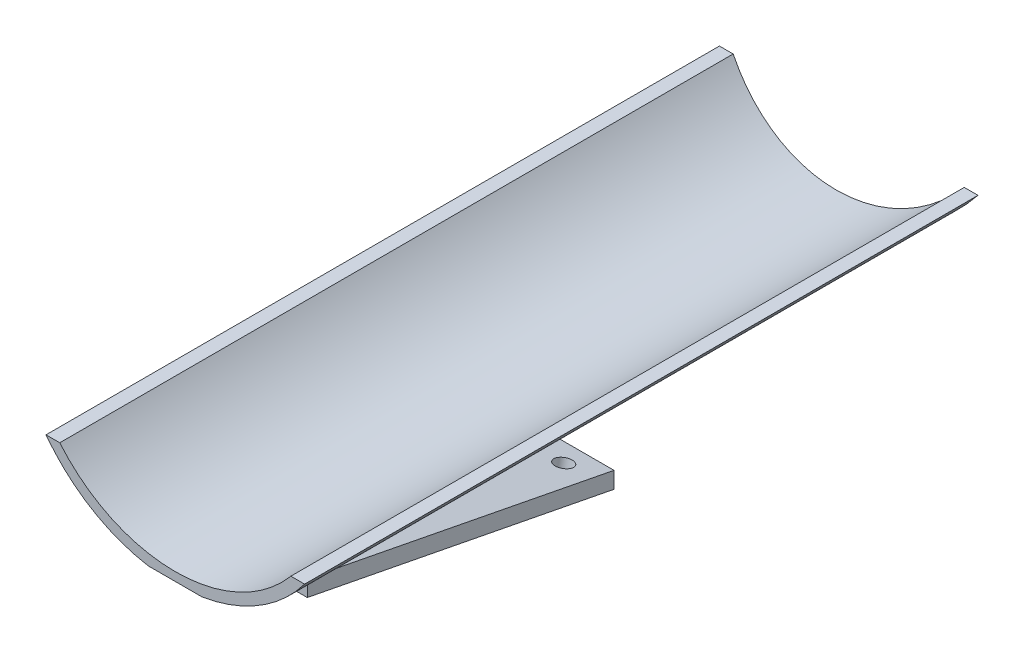
SolidWorks part; units mm, degrees
ref_plane "Front Plane" through (0, 0, 0) normal (0, 0, 1) x (1, 0, 0)
ref_plane "Top Plane" through (0, 0, 0) normal (0, 1, 0) x (1, 0, 0)
ref_plane "Right Plane" through (0, 0, 0) normal (1, 0, 0) x (0, 0, -1)
ref_axis "Axis1" through (0, -34.3594, 0) along (0, 1, 0)
ref_axis "Axis2" through (-26.4, 0, 0) along (1, 0, 0)
sketch "Sketch1" plane through (0, 0, 0) normal (0, 0, 1) x (1, 0, 0)
  line L0 (-24, 0) -> (-21.4476, 0)
  line L1 (21.4476, 0) -> (24, 0)
  line L2 (5, -11.5804) -> (-5, -11.5804)
  arc A0 (-24, 0) -> (-5, -11.5804) centre (0, 18) ccw
  arc A1 (21.4476, 0) -> (-21.4476, 0) centre (0, 18) cw
  arc A2 (5, -11.5804) -> (24, 0) centre (0, 18) ccw
  dimension "D1" = 28
  dimension "D2" = 30
  dimension "D3" = 18
  dimension "D4" = 10
extrude "Main" add sketch "Sketch1" along normal blind 125
ref_plane "CutPlane" through (0, 0, 0) normal (0, 0.225, 0.9744) x (1, 0, 0)
sketch "Sketch2" plane through (0, 0, 0) normal (0, 0.225, 0.9744) x (1, 0, 0)
  circle A0 centre (0, 0) radius 25
  point P2 (0.8432, 0)
  point P3 (0, 0)
  dimension "D1" = 50
extrude "BehindCut" cut sketch "Sketch2" against normal through all
sketch "Sketch4" plane through (0, 0, 0) normal (1, 0, 0) x (0, 0, -1)
  line L0 (-113, -11.5804) -> (-56.0656, -11.5804)
  line L1 (-56.0656, -11.5804) -> (-56.0656, -24.9799)
  line L2 (-56.0656, -24.9799) -> (-113, -13.913)
  line L3 (-113, -13.913) -> (-113, -11.5804)
  line L5 (-2.6735, -11.5804) -> (-2.6735, -35.3583) construction
  line L6 (6.5326, 28.2957) -> (-6.5326, -28.2957) construction
  line L7 (-125, -11.5804) -> (-2.6735, -11.5804) construction
  point P2 (-3.3421, -11.5804)
  point P6 (-2.1955, -11.5804)
  point P7 (-56.2674, -11.5804)
  point P8 (-56.2674, -25.3258)
  point P15 (-3.198, -38.6492)
  point P16 (0, 0)
  point P17 (-115.3775, -11.5804)
  point P19 (-45.7608, -32.001)
  point P20 (-105, -11.5804)
  point P21 (-45.7838, -11.5804)
  point P22 (0, 0)
  point P23 (0, 0)
  point P25 (-56.2674, -25.3258)
  point P26 (-56.2674, -11.5804)
  point P29 (-113, -13.2669)
  point P30 (-113, -11.5804)
  point P31 (-113, -13.4538)
  dimension "D1" = 11
  dimension "D2" = 58
  dimension "D3" = 12
  dimension "D4" = 23.7779
  dimension "D5" = 13.3995
extrude "CentralSupport" add sketch "Sketch4" along normal mid plane 5
sketch "Sketch5" plane through (0, 0, 0) normal (1, 0, 0) x (0, 0, -1)
  line L0 (-56.0656, -24.9799) -> (-113, -13.913)
  line L1 (-113, -13.913) -> (-113, -11.5804)
  line L2 (-109.2775, -11.5804) -> (-56.0656, -21.9237)
  line L3 (-113, -13.913) -> (-56.0656, -24.9799) construction
  line L4 (-56.0656, -21.9237) -> (-56.0656, -24.9799)
  line L5 (-56.0656, -24.9799) -> (-56.0656, -11.5804) construction
  line L9 (-56.0656, -11.5804) -> (-113, -11.5804) construction
  line L10 (-113, -11.5804) -> (-109.2775, -11.5804)
  line L11 (-113, -11.5804) -> (-113, -13.913) construction
  point P6 (-113, -12.087)
  point P11 (-56.0656, -24.3163)
  point P12 (-56.0656, -24.9247)
  point P15 (-56.0656, -24.9799)
  dimension "D2" = 3
extrude "SideSupport" add sketch "Sketch5" along normal mid plane 25
sketch "Sketch6" plane through (0, -34.5717, 6.7201) normal (0, -0.9816, 0.1908) x (-1, 0, 0)
  line L0 (-2.5, -120.4938) -> (-2.5, -50.2692) construction
  line L1 (-12.5, -50.2692) -> (12.5, -50.2692) construction
  line L2 (2.5, -120.4938) -> (2.5, -50.2692) construction
  circle A0 centre (7.5, -55.2692) radius 1.6
  circle A1 centre (-7.5, -55.2692) radius 1.6
  point P4 (0, 0)
  dimension "D1" = 3.2
  dimension "D2" = 5
  dimension "D3" = 5
  dimension "D4" = 5
extrude "HoleFix" cut sketch "Sketch6" against normal up to next
sketch "Sketch9" plane through (0, -34.5717, 6.7201) normal (0, -0.9816, 0.1908) x (-1, 0, 0)
  line L0 (-12.5, -50.2692) -> (12.5, -50.2692) construction
  line L1 (2.5, -50.2692) -> (-2.5, -50.2692)
  line L2 (2.5, -50.2692) -> (2.5, -108.2692)
  line L3 (2.5, -108.2692) -> (-2.5, -108.2692)
  line L4 (-2.5, -50.2692) -> (-2.5, -108.2692)
  line L5 (-12.5, -108.2692) -> (12.5, -108.2692) construction
  line L6 (2.5, -50.8523) -> (2.5, -52.8259) construction
  line L7 (-2.5, -50.8523) -> (-2.5, -52.8259) construction
extrude "Boss-Extrude4" add sketch "Sketch9" along normal blind 3
